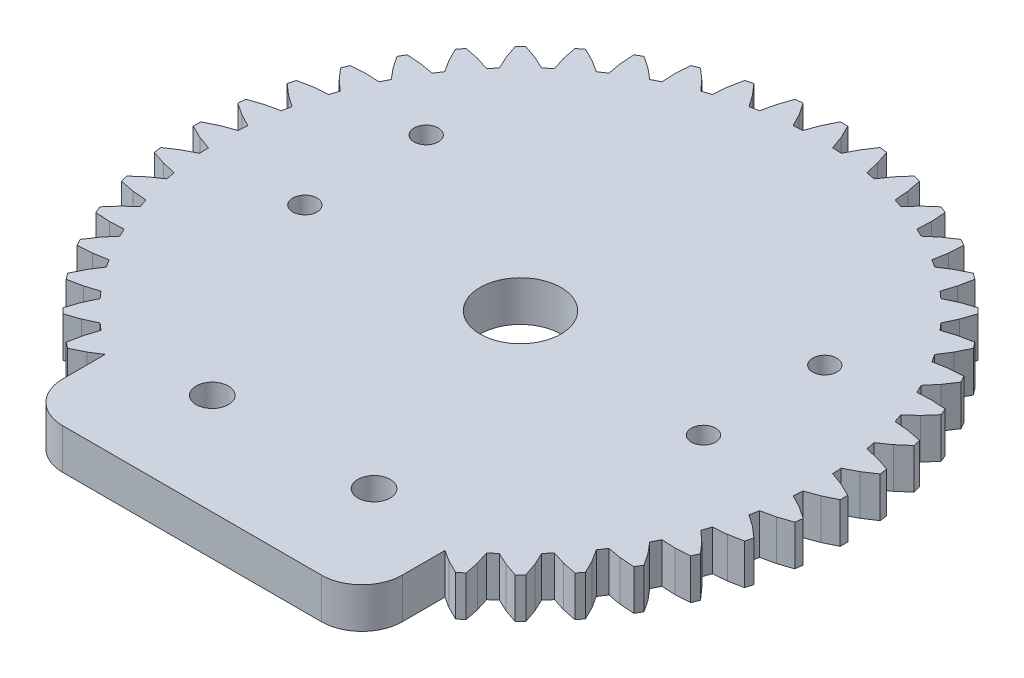
SolidWorks part; units mm, degrees
material "Acrylic (Medium-high impact)"
ref_plane "Front Plane" through (0, 0, 0) normal (0, 0, 1) x (1, 0, 0)
ref_plane "Top Plane" through (0, 0, 0) normal (0, 1, 0) x (1, 0, 0)
ref_plane "Right Plane" through (0, 0, 0) normal (1, 0, 0) x (0, 0, -1)
sketch "Sketch2" plane through (0, 0, 0) normal (0, 1, 0) x (1, 0, 0)
  line L0 (83.8835, 67.191) -> (85.5092, 66.6061)
  line L1 (85.5092, 66.6061) -> (87.1271, 65.8138)
  line L2 (87.1271, 65.8138) -> (87.1271, 64.8854)
  line L3 (87.1271, 64.8854) -> (85.5092, 64.0931)
  line L4 (85.5092, 64.0931) -> (83.8835, 63.5083)
  line L5 (83.8835, 63.5083) -> (83.8095, 62.3776)
  line L6 (83.8095, 62.3776) -> (85.3448, 61.5855)
  line L7 (85.3448, 61.5855) -> (86.8456, 60.5888)
  line L8 (86.8456, 60.5888) -> (86.7243, 59.6683)
  line L9 (86.7243, 59.6683) -> (85.0168, 59.094)
  line L10 (85.0168, 59.094) -> (83.3288, 58.7263)
  line L11 (83.3288, 58.7263) -> (83.1077, 57.615)
  line L12 (83.1077, 57.615) -> (84.5266, 56.6293)
  line L13 (84.5266, 56.6293) -> (85.8844, 55.4453)
  line L14 (85.8844, 55.4453) -> (85.6441, 54.5485)
  line L15 (85.6441, 54.5485) -> (83.8761, 54.202)
  line L16 (83.8761, 54.202) -> (82.1545, 54.0577)
  line L17 (82.1545, 54.0577) -> (81.7903, 52.9848)
  line L18 (81.7903, 52.9848) -> (83.0684, 51.8222)
  line L19 (83.0684, 51.8222) -> (84.26, 50.4711)
  line L20 (84.26, 50.4711) -> (83.9048, 49.6134)
  line L21 (83.9048, 49.6134) -> (82.1066, 49.5006)
  line L22 (82.1066, 49.5006) -> (80.3809, 49.5823)
  line L23 (80.3809, 49.5823) -> (79.8799, 48.5661)
  line L24 (79.8799, 48.5661) -> (80.9952, 47.2468)
  line L25 (80.9952, 47.2468) -> (82.0003, 45.7516)
  line L26 (82.0003, 45.7516) -> (81.5361, 44.9476)
  line L27 (81.5361, 44.9476) -> (79.7387, 45.0704)
  line L28 (79.7387, 45.0704) -> (78.0384, 45.3766)
  line L29 (78.0384, 45.3766) -> (77.4089, 44.4346)
  line L30 (77.4089, 44.4346) -> (78.3426, 42.9809)
  line L31 (78.3426, 42.9809) -> (79.1439, 41.3674)
  line L32 (79.1439, 41.3674) -> (78.5788, 40.6309)
  line L33 (78.5788, 40.6309) -> (76.8128, 40.9873)
  line L34 (76.8128, 40.9873) -> (75.167, 41.5128)
  line L35 (75.167, 41.5128) -> (74.4199, 40.6609)
  line L36 (74.4199, 40.6609) -> (75.1558, 39.0979)
  line L37 (75.1558, 39.0979) -> (75.7397, 37.3936)
  line L38 (75.7397, 37.3936) -> (75.0832, 36.737)
  line L39 (75.0832, 36.737) -> (73.3788, 37.3209)
  line L40 (73.3788, 37.3209) -> (71.8158, 38.0569)
  line L41 (71.8158, 38.0569) -> (70.9639, 37.3097)
  line L42 (70.9639, 37.3097) -> (71.4895, 35.6639)
  line L43 (71.4895, 35.6639) -> (71.8459, 33.898)
  line L44 (71.8459, 33.898) -> (71.1093, 33.3328)
  line L45 (71.1093, 33.3328) -> (69.4958, 34.1341)
  line L46 (69.4958, 34.1341) -> (68.0421, 35.0679)
  line L47 (68.0421, 35.0679) -> (67.1001, 34.4384)
  line L48 (67.1001, 34.4384) -> (67.4064, 32.738)
  line L49 (67.4064, 32.738) -> (67.5292, 30.9407)
  line L50 (67.5292, 30.9407) -> (66.7251, 30.4764)
  line L51 (66.7251, 30.4764) -> (65.23, 31.4815)
  line L52 (65.23, 31.4815) -> (63.9107, 32.5969)
  line L53 (63.9107, 32.5969) -> (62.8945, 32.0958)
  line L54 (62.8945, 32.0958) -> (62.9762, 30.3701)
  line L55 (62.9762, 30.3701) -> (62.8633, 28.572)
  line L56 (62.8633, 28.572) -> (62.0056, 28.2167)
  line L57 (62.0056, 28.2167) -> (60.6545, 29.4083)
  line L58 (60.6545, 29.4083) -> (59.4919, 30.6864)
  line L59 (59.4919, 30.6864) -> (58.419, 30.3222)
  line L60 (58.419, 30.3222) -> (58.2748, 28.6006)
  line L61 (58.2748, 28.6006) -> (57.9283, 26.8327)
  line L62 (57.9283, 26.8327) -> (57.0315, 26.5924)
  line L63 (57.0315, 26.5924) -> (55.8474, 27.9502)
  line L64 (55.8474, 27.9502) -> (54.8618, 29.369)
  line L65 (54.8618, 29.369) -> (53.7504, 29.1479)
  line L66 (53.7504, 29.1479) -> (53.3827, 27.4599)
  line L67 (53.3827, 27.4599) -> (52.8084, 25.7524)
  line L68 (52.8084, 25.7524) -> (51.888, 25.6311)
  line L69 (51.888, 25.6311) -> (50.8913, 27.1319)
  line L70 (50.8913, 27.1319) -> (50.0992, 28.6672)
  line L71 (50.0992, 28.6672) -> (48.9685, 28.5932)
  line L72 (48.9685, 28.5932) -> (48.3836, 26.9675)
  line L73 (48.3836, 26.9675) -> (47.5914, 25.3496)
  line L74 (47.5914, 25.3496) -> (46.6629, 25.3496)
  line L75 (46.6629, 25.3496) -> (45.8707, 26.9675)
  line L76 (45.8707, 26.9675) -> (45.2858, 28.5932)
  line L77 (45.2858, 28.5932) -> (44.1551, 28.6672)
  line L78 (44.1551, 28.6672) -> (43.363, 27.1319)
  line L79 (43.363, 27.1319) -> (42.3663, 25.6311)
  line L80 (42.3663, 25.6311) -> (41.4459, 25.7524)
  line L81 (41.4459, 25.7524) -> (40.8715, 27.4599)
  line L82 (40.8715, 27.4599) -> (40.5038, 29.1479)
  line L83 (40.5038, 29.1479) -> (39.3925, 29.369)
  line L84 (39.3925, 29.369) -> (38.4068, 27.9502)
  line L85 (38.4068, 27.9502) -> (37.2228, 26.5924)
  line L86 (37.2228, 26.5924) -> (36.326, 26.8327)
  line L87 (36.326, 26.8327) -> (35.9795, 28.6006)
  line L88 (35.9795, 28.6006) -> (35.8352, 30.3222)
  line L89 (35.8352, 30.3222) -> (34.7624, 30.6864)
  line L90 (34.7624, 30.6864) -> (33.5998, 29.4083)
  line L91 (33.5998, 29.4083) -> (32.2487, 28.2167)
  line L92 (32.2487, 28.2167) -> (31.3909, 28.572)
  line L93 (31.3909, 28.572) -> (31.2781, 30.3701)
  line L94 (31.2781, 30.3701) -> (31.3598, 32.0958)
  line L95 (31.3598, 32.0958) -> (30.3436, 32.5969)
  line L96 (30.3436, 32.5969) -> (29.0243, 31.4815)
  line L97 (29.0243, 31.4815) -> (27.5292, 30.4764)
  line L98 (27.5292, 30.4764) -> (26.7251, 30.9407)
  line L99 (26.7251, 30.9407) -> (26.8479, 32.738)
  line L100 (26.8479, 32.738) -> (27.1541, 34.4384)
  line L101 (27.1541, 34.4384) -> (26.2121, 35.0679)
  line L102 (26.2121, 35.0679) -> (24.7585, 34.1341)
  line L103 (24.7585, 34.1341) -> (23.1449, 33.3328)
  line L104 (23.1449, 33.3328) -> (22.4084, 33.898)
  line L105 (22.4084, 33.898) -> (22.7648, 35.6639)
  line L106 (22.7648, 35.6639) -> (23.2904, 37.3097)
  line L107 (23.2904, 37.3097) -> (22.4384, 38.0569)
  line L108 (22.4384, 38.0569) -> (20.8754, 37.3209)
  line L109 (20.8754, 37.3209) -> (19.1711, 36.737)
  line L110 (19.1711, 36.737) -> (18.5146, 37.3936)
  line L111 (18.5146, 37.3936) -> (19.0984, 39.0979)
  line L112 (19.0984, 39.0979) -> (19.8344, 40.6609)
  line L113 (19.8344, 40.6609) -> (19.0872, 41.5128)
  line L114 (19.0872, 41.5128) -> (17.4414, 40.9873)
  line L115 (17.4414, 40.9873) -> (15.6755, 40.6309)
  line L116 (15.6755, 40.6309) -> (15.1103, 41.3674)
  line L117 (15.1103, 41.3674) -> (15.9116, 42.9809)
  line L118 (15.9116, 42.9809) -> (16.8454, 44.4346)
  line L119 (16.8454, 44.4346) -> (16.2159, 45.3766)
  line L120 (16.2159, 45.3766) -> (14.5155, 45.0704)
  line L121 (14.5155, 45.0704) -> (12.7182, 44.9476)
  line L122 (12.7182, 44.9476) -> (12.2539, 45.7516)
  line L123 (12.2539, 45.7516) -> (13.2591, 47.2468)
  line L124 (13.2591, 47.2468) -> (14.3744, 48.5661)
  line L125 (14.3744, 48.5661) -> (13.8733, 49.5823)
  line L126 (13.8733, 49.5823) -> (12.1476, 49.5006)
  line L127 (12.1476, 49.5006) -> (10.3495, 49.6134)
  line L128 (10.3495, 49.6134) -> (9.9942, 50.4711)
  line L129 (9.9942, 50.4711) -> (11.1858, 51.8222)
  line L130 (11.1858, 51.8222) -> (12.4639, 52.9848)
  line L131 (12.4639, 52.9848) -> (12.0997, 54.0577)
  line L132 (12.0997, 54.0577) -> (10.3781, 54.202)
  line L133 (10.3781, 54.202) -> (8.6102, 54.5485)
  line L134 (8.6102, 54.5485) -> (8.3699, 55.4453)
  line L135 (8.3699, 55.4453) -> (9.7277, 56.6293)
  line L136 (9.7277, 56.6293) -> (11.1465, 57.615)
  line L137 (11.1465, 57.615) -> (10.9255, 58.7263)
  line L138 (10.9255, 58.7263) -> (9.2374, 59.094)
  line L139 (9.2374, 59.094) -> (7.5299, 59.6683)
  line L140 (7.5299, 59.6683) -> (7.4086, 60.5888)
  line L141 (7.4086, 60.5888) -> (8.9094, 61.5855)
  line L142 (8.9094, 61.5855) -> (10.4448, 62.3776)
  line L143 (10.4448, 62.3776) -> (10.3707, 63.5083)
  line L144 (10.3707, 63.5083) -> (8.745, 64.0931)
  line L145 (8.745, 64.0931) -> (7.1271, 64.8854)
  line L146 (7.1271, 64.8854) -> (7.1271, 65.8138)
  line L147 (7.1271, 65.8138) -> (8.745, 66.6061)
  line L148 (8.745, 66.6061) -> (10.3707, 67.191)
  line L149 (10.3707, 67.191) -> (10.4448, 68.3216)
  line L150 (10.4448, 68.3216) -> (8.9094, 69.1138)
  line L151 (8.9094, 69.1138) -> (7.4086, 70.1105)
  line L152 (7.4086, 70.1105) -> (7.5299, 71.0309)
  line L153 (7.5299, 71.0309) -> (9.2374, 71.6052)
  line L154 (9.2374, 71.6052) -> (10.9255, 71.9729)
  line L155 (10.9255, 71.9729) -> (11.1465, 73.0842)
  line L156 (11.1465, 73.0842) -> (9.7277, 74.0699)
  line L157 (9.7277, 74.0699) -> (8.3699, 75.254)
  line L158 (8.3699, 75.254) -> (8.6102, 76.1508)
  line L159 (8.6102, 76.1508) -> (10.3781, 76.4973)
  line L160 (10.3781, 76.4973) -> (12.0997, 76.6415)
  line L161 (12.0997, 76.6415) -> (12.4639, 77.7144)
  line L162 (12.4639, 77.7144) -> (11.1858, 78.877)
  line L163 (11.1858, 78.877) -> (9.9942, 80.2281)
  line L164 (9.9942, 80.2281) -> (10.3495, 81.0858)
  line L165 (10.3495, 81.0858) -> (12.1476, 81.1987)
  line L166 (12.1476, 81.1987) -> (13.8733, 81.117)
  line L167 (13.8733, 81.117) -> (14.3744, 82.1332)
  line L168 (14.3744, 82.1332) -> (13.2591, 83.4525)
  line L169 (13.2591, 83.4525) -> (12.2539, 84.9476)
  line L170 (12.2539, 84.9476) -> (12.7182, 85.7516)
  line L171 (12.7182, 85.7516) -> (14.5155, 85.6289)
  line L172 (14.5155, 85.6289) -> (16.2159, 85.3226)
  line L173 (16.2159, 85.3226) -> (16.8454, 86.2646)
  line L174 (16.8454, 86.2646) -> (15.9116, 87.7183)
  line L175 (15.9116, 87.7183) -> (15.1103, 89.3318)
  line L176 (15.1103, 89.3318) -> (15.6755, 90.0684)
  line L177 (15.6755, 90.0684) -> (17.4414, 89.712)
  line L178 (17.4414, 89.712) -> (19.0872, 89.1864)
  line L179 (19.0872, 89.1864) -> (19.8344, 90.0383)
  line L180 (19.8344, 90.0383) -> (19.0984, 91.6013)
  line L181 (19.0984, 91.6013) -> (18.5146, 93.3057)
  line L182 (18.5146, 93.3057) -> (19.1711, 93.9622)
  line L183 (19.1711, 93.9622) -> (20.8754, 93.3783)
  line L184 (20.8754, 93.3783) -> (22.4384, 92.6424)
  line L185 (22.4384, 92.6424) -> (23.2904, 93.3895)
  line L186 (23.2904, 93.3895) -> (22.7648, 95.0353)
  line L187 (22.7648, 95.0353) -> (22.4084, 96.8013)
  line L188 (22.4084, 96.8013) -> (23.1449, 97.3664)
  line L189 (23.1449, 97.3664) -> (24.7585, 96.5651)
  line L190 (24.7585, 96.5651) -> (26.2121, 95.6314)
  line L191 (26.2121, 95.6314) -> (27.1541, 96.2609)
  line L192 (27.1541, 96.2609) -> (26.8479, 97.9612)
  line L193 (26.8479, 97.9612) -> (26.7251, 99.7586)
  line L194 (26.7251, 99.7586) -> (27.5292, 100.2228)
  line L195 (27.5292, 100.2228) -> (29.0243, 99.2177)
  line L196 (29.0243, 99.2177) -> (30.3436, 98.1023)
  line L197 (30.3436, 98.1023) -> (31.3598, 98.6034)
  line L198 (31.3598, 98.6034) -> (31.2781, 100.3291)
  line L199 (31.2781, 100.3291) -> (31.3909, 102.1272)
  line L200 (31.3909, 102.1272) -> (32.2487, 102.4825)
  line L201 (32.2487, 102.4825) -> (33.5998, 101.2909)
  line L202 (33.5998, 101.2909) -> (34.7624, 100.0128)
  line L203 (34.7624, 100.0128) -> (35.8352, 100.377)
  line L204 (35.8352, 100.377) -> (35.9795, 102.0986)
  line L205 (35.9795, 102.0986) -> (36.326, 103.8666)
  line L206 (36.326, 103.8666) -> (37.2228, 104.1068)
  line L207 (37.2228, 104.1068) -> (38.4068, 102.7491)
  line L208 (38.4068, 102.7491) -> (39.3925, 101.3302)
  line L209 (39.3925, 101.3302) -> (40.5038, 101.5513)
  line L210 (40.5038, 101.5513) -> (40.8715, 103.2393)
  line L211 (40.8715, 103.2393) -> (41.4459, 104.9468)
  line L212 (41.4459, 104.9468) -> (42.3663, 105.0681)
  line L213 (42.3663, 105.0681) -> (43.363, 103.5673)
  line L214 (43.363, 103.5673) -> (44.1551, 102.032)
  line L215 (44.1551, 102.032) -> (45.2858, 102.106)
  line L216 (45.2858, 102.106) -> (45.8707, 103.7317)
  line L217 (45.8707, 103.7317) -> (46.6629, 105.3496)
  line L218 (46.6629, 105.3496) -> (47.5914, 105.3496)
  line L219 (47.5914, 105.3496) -> (48.3836, 103.7317)
  line L220 (48.3836, 103.7317) -> (48.9685, 102.106)
  line L221 (48.9685, 102.106) -> (50.0992, 102.032)
  line L222 (50.0992, 102.032) -> (50.8913, 103.5673)
  line L223 (50.8913, 103.5673) -> (51.888, 105.0681)
  line L224 (51.888, 105.0681) -> (52.8084, 104.9468)
  line L225 (52.8084, 104.9468) -> (53.3827, 103.2393)
  line L226 (53.3827, 103.2393) -> (53.7504, 101.5513)
  line L227 (53.7504, 101.5513) -> (54.8618, 101.3302)
  line L228 (54.8618, 101.3302) -> (55.8474, 102.7491)
  line L229 (55.8474, 102.7491) -> (57.0315, 104.1068)
  line L230 (57.0315, 104.1068) -> (57.9283, 103.8666)
  line L231 (57.9283, 103.8666) -> (58.2748, 102.0986)
  line L232 (58.2748, 102.0986) -> (58.419, 100.377)
  line L233 (58.419, 100.377) -> (59.4919, 100.0128)
  line L234 (59.4919, 100.0128) -> (60.6545, 101.2909)
  line L235 (60.6545, 101.2909) -> (62.0056, 102.4825)
  line L236 (62.0056, 102.4825) -> (62.8633, 102.1272)
  line L237 (62.8633, 102.1272) -> (62.9762, 100.3291)
  line L238 (62.9762, 100.3291) -> (62.8945, 98.6034)
  line L239 (62.8945, 98.6034) -> (63.9107, 98.1023)
  line L240 (63.9107, 98.1023) -> (65.23, 99.2177)
  line L241 (65.23, 99.2177) -> (66.7251, 100.2228)
  line L242 (66.7251, 100.2228) -> (67.5292, 99.7586)
  line L243 (67.5292, 99.7586) -> (67.4064, 97.9612)
  line L244 (67.4064, 97.9612) -> (67.1001, 96.2609)
  line L245 (67.1001, 96.2609) -> (68.0421, 95.6314)
  line L246 (68.0421, 95.6314) -> (69.4958, 96.5651)
  line L247 (69.4958, 96.5651) -> (71.1093, 97.3664)
  line L248 (71.1093, 97.3664) -> (71.8459, 96.8013)
  line L249 (71.8459, 96.8013) -> (71.4895, 95.0353)
  line L250 (71.4895, 95.0353) -> (70.9639, 93.3895)
  line L251 (70.9639, 93.3895) -> (71.8158, 92.6424)
  line L252 (71.8158, 92.6424) -> (73.3788, 93.3783)
  line L253 (73.3788, 93.3783) -> (75.0832, 93.9622)
  line L254 (75.0832, 93.9622) -> (75.7397, 93.3057)
  line L255 (75.7397, 93.3057) -> (75.1558, 91.6013)
  line L256 (75.1558, 91.6013) -> (74.4199, 90.0383)
  line L257 (74.4199, 90.0383) -> (75.167, 89.1864)
  line L258 (75.167, 89.1864) -> (76.8128, 89.712)
  line L259 (76.8128, 89.712) -> (78.5788, 90.0684)
  line L260 (78.5788, 90.0684) -> (79.1439, 89.3318)
  line L261 (79.1439, 89.3318) -> (78.3426, 87.7183)
  line L262 (78.3426, 87.7183) -> (77.4089, 86.2646)
  line L263 (77.4089, 86.2646) -> (78.0384, 85.3226)
  line L264 (78.0384, 85.3226) -> (79.7387, 85.6289)
  line L265 (79.7387, 85.6289) -> (81.5361, 85.7516)
  line L266 (81.5361, 85.7516) -> (82.0003, 84.9476)
  line L267 (82.0003, 84.9476) -> (80.9952, 83.4525)
  line L268 (80.9952, 83.4525) -> (79.8799, 82.1332)
  line L269 (79.8799, 82.1332) -> (80.3809, 81.117)
  line L270 (80.3809, 81.117) -> (82.1066, 81.1987)
  line L271 (82.1066, 81.1987) -> (83.9048, 81.0858)
  line L272 (83.9048, 81.0858) -> (84.26, 80.2281)
  line L273 (84.26, 80.2281) -> (83.0684, 78.877)
  line L274 (83.0684, 78.877) -> (81.7903, 77.7144)
  line L275 (81.7903, 77.7144) -> (82.1545, 76.6415)
  line L276 (82.1545, 76.6415) -> (83.8761, 76.4973)
  line L277 (83.8761, 76.4973) -> (85.6441, 76.1508)
  line L278 (85.6441, 76.1508) -> (85.8844, 75.254)
  line L279 (85.8844, 75.254) -> (84.5266, 74.0699)
  line L280 (84.5266, 74.0699) -> (83.1077, 73.0842)
  line L281 (83.1077, 73.0842) -> (83.3288, 71.9729)
  line L282 (83.3288, 71.9729) -> (85.0168, 71.6052)
  line L283 (85.0168, 71.6052) -> (86.7243, 71.0309)
  line L284 (86.7243, 71.0309) -> (86.8456, 70.1105)
  line L285 (86.8456, 70.1105) -> (85.3448, 69.1138)
  line L286 (85.3448, 69.1138) -> (83.8095, 68.3216)
  line L287 (83.8095, 68.3216) -> (83.8835, 67.191)
  line L288 (47.1271, 105.3496) -> (47.1271, 25.3496) construction
  line L289 (7.1271, 65.3496) -> (87.1271, 65.3496) construction
  circle A0 centre (47.1271, 65.3496) radius 5
  point P292 (47.1271, 65.3496)
  dimension "D1" = 10
sketch "Sketch7" plane through (0, 0, 0) normal (0, 1, 0) x (1, 0, 0)
  line L0 (47.1271, 65.3496) -> (47.1271, 5.5554) construction
  line L1 (47.1271, 105.3496) -> (47.1271, 25.3496) construction
  circle A0 centre (37.1271, 37.2366) radius 2
  circle A1 centre (57.1271, 37.2366) radius 2
  dimension "D3" = 4
  dimension "D1" = 20
  dimension "D2" = 28.113
sketch "Sketch8" plane through (0, 0, 0) normal (0, 1, 0) x (1, 0, 0)
  line L0 (37.1271, 37.2366) -> (57.1271, 37.2366) construction
  line L2 (26.1271, 49.7366) -> (68.1271, 49.7366)
  line L3 (26.1271, 49.7366) -> (26.1271, 24.7366)
  line L4 (26.1271, 24.7366) -> (68.1271, 24.7366)
  line L5 (68.1271, 49.7366) -> (68.1271, 24.7366)
  line L6 (26.1271, 49.7366) -> (68.1271, 24.7366) construction
  line L7 (26.1271, 24.7366) -> (68.1271, 49.7366) construction
  point P4 (47.1271, 37.2366)
  dimension "D1" = 42
  dimension "D2" = 25
extrude "Boss-Extrude3" add sketch "Sketch2" along normal blind 5
extrude "Boss-Extrude4" add sketch "Sketch8" along normal up to surface (5 mm away) up to face at (47.1271, 5, -65.3496)
extrude "Cut-Extrude1" cut sketch "Sketch7" along normal through all
sketch "Sketch10" plane through (0, 0, 0) normal (0, -1, 0) x (1, 0, 0)
  circle A0 centre (71.7588, -78.3415) radius 1.5
  circle A1 centre (71.7588, -63.3415) radius 1.5
  circle A2 centre (22.4704, -78.3415) radius 1.5
  circle A3 centre (22.4704, -63.3415) radius 1.5
  circle A4 centre (71.7588, -78.3415) radius 1.5 construction
extrude "Cut-Extrude2" cut sketch "Sketch10" against normal up to next
fillet "Fillet1" radius 5 2 edges at (68.1271, 2.5, -24.7366) (26.1271, 2.5, -24.7366)
ref_axis "Axis5" through (47.1271, 5, -65.3496) along (0, -1, 0)
